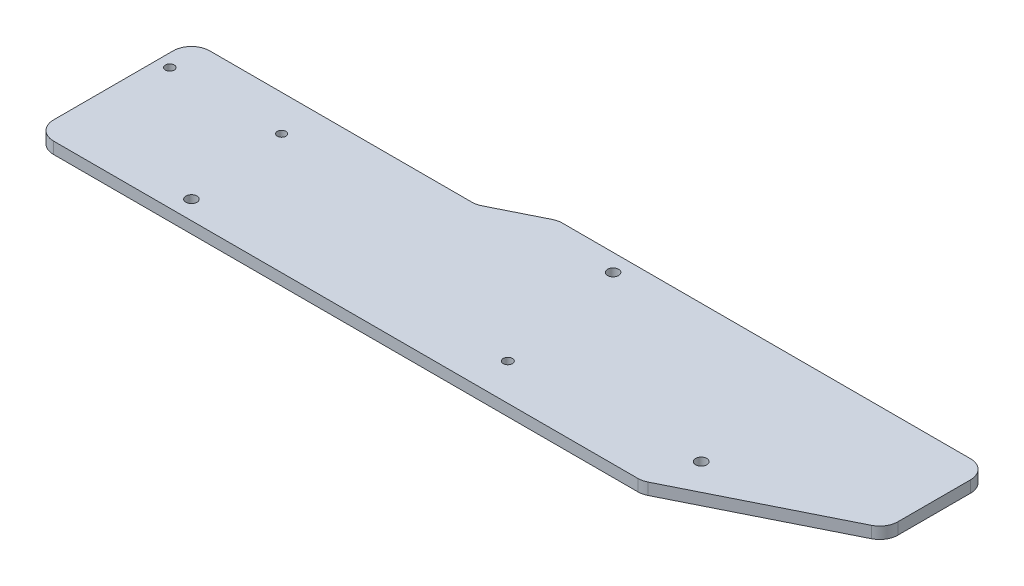
SolidWorks part; units mm, degrees
ref_plane "Front" through (0, 0, 0) normal (0, 0, 1) x (1, 0, 0)
ref_plane "Top" through (0, 0, 0) normal (0, 1, 0) x (1, 0, 0)
ref_plane "Right" through (0, 0, 0) normal (1, 0, 0) x (0, 0, -1)
sketch "Sketch1" plane through (0, 0, 0) normal (0, 1, 0) x (1, 0, 0)
  line L1 (0, 0) -> (210, 0)
  line L2 (0, 0) -> (0, -50)
  line L3 (0, -50) -> (210, -50)
  line L4 (210, 0) -> (210, -50)
  circle A7 centre (3.4895, -16.7877) radius 1.2117
  circle A8 centre (34.3726, -17.194) radius 1.1656
  circle A9 centre (37.5207, -44.9212) radius 1.5
  circle A10 centre (118.879, -40.0177) radius 1.25
  circle A11 centre (112.3021, -4.7393) radius 1.5
  circle A12 centre (168.9752, -37.4032) radius 1.5173
  dimension "D1" = 210
  dimension "D2" = 50
extrude "Boss-Extrude1" add sketch "Sketch1" along normal blind 3.175
sketch "Sketch10" plane through (0, 3.175, 0) normal (0, 1, 0) x (1, 0, 0)
  line L0 (210, -27.8594) -> (165.5029, -50)
  line L1 (210, -50) -> (210, 0) construction
  line L2 (0, -50) -> (210, -50) construction
  line L3 (165.5029, -50) -> (210, -50)
  line L4 (210, -50) -> (210, -27.8594)
  line L5 (92.5326, 0) -> (77.6548, -7.4028)
  line L6 (210, 0) -> (0, 0) construction
  line L7 (77.6548, -7.4028) -> (0, -7.4028)
  line L8 (0, 0) -> (0, -50) construction
  line L9 (0, -7.4028) -> (0, 0)
  line L10 (0, 0) -> (92.5326, 0)
extrude "Cut-Extrude7" cut sketch "Sketch10" against normal blind 10
fillet "Fillet3" radius 5 7 edges at (0, 1.5875, 50) (0, 1.5875, 7.4028) (77.6548, 1.5875, 7.4028) (92.5326, 1.5875, 0) (210, 1.5875, 0) (210, 1.5875, 27.8594) (165.5029, 1.5875, 50)
